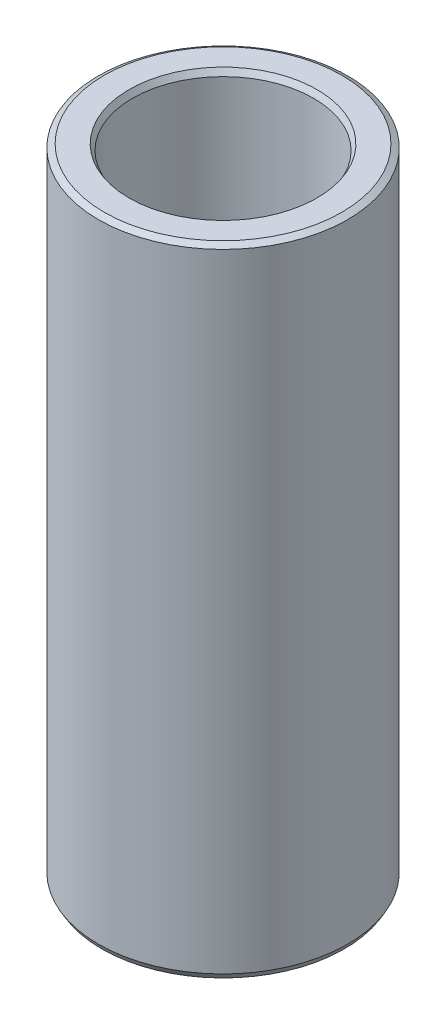
SolidWorks part; units mm, degrees
ref_plane "Front Plane" through (0, 0, 0) normal (0, 0, 1) x (1, 0, 0)
ref_plane "Top Plane" through (0, 0, 0) normal (0, 1, 0) x (1, 0, 0)
ref_plane "Right Plane" through (0, 0, 0) normal (1, 0, 0) x (0, 0, -1)
sketch "Sketch1" plane through (0, 0, 0) normal (0, 1, 0) x (1, 0, 0)
  circle A0 centre (0, 0) radius 60
  dimension "SLEEVE_OD" = 120
extrude "Boss-Extrude1" add sketch "Sketch1" along normal blind 306.5681
sketch "Sketch2" plane through (0, 0, 0) normal (0, 1, 0) x (1, 0, 0)
  circle A0 centre (0, 0) radius 43.605
  dimension "BORE_D" = 87.2099
extrude "Cut-Extrude1" cut sketch "Sketch2" along normal through all
chamfer "Chamfer1" distance 1.63 angle 60 4 edges at (0, 306.5681, 43.605) (0, 0, 43.605) (0, 0, 60) (0, 306.5681, 60) first distance on face at (0, 306.5681, 43.605) first distance on face at (0, 0, 43.605) first distance on face at (0, 306.5681, 60)
